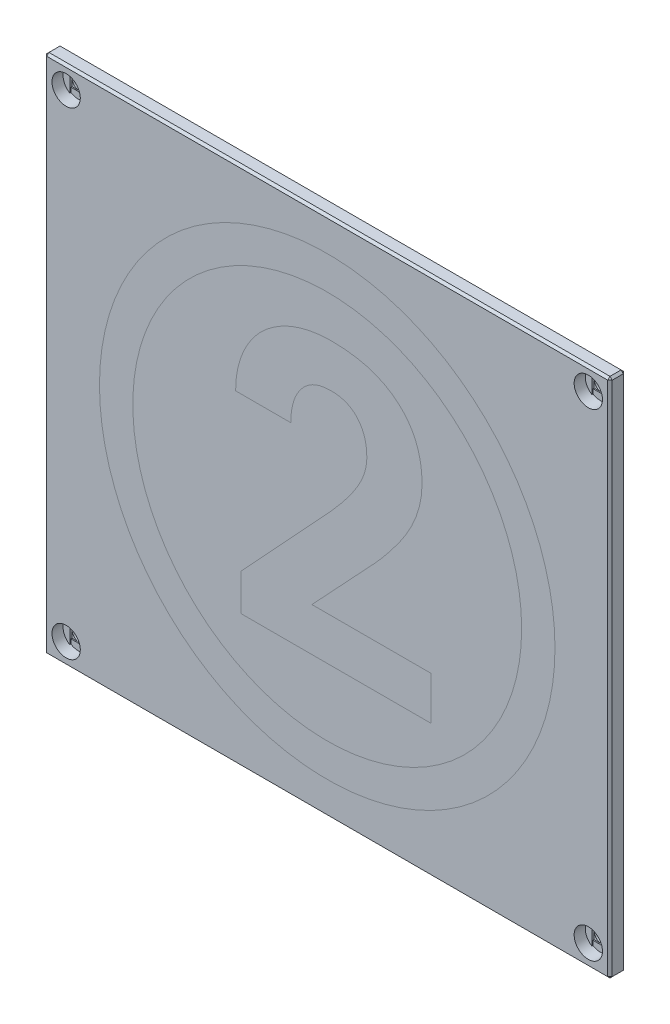
SolidWorks part; units mm, degrees
ref_plane "Front Plane" through (0, 0, 0) normal (0, 0, 1) x (1, 0, 0)
ref_plane "Top Plane" through (0, 0, 0) normal (0, 1, 0) x (1, 0, 0)
ref_plane "Right Plane" through (0, 0, 0) normal (1, 0, 0) x (0, 0, -1)
sketch "Sketch1" plane through (0, 0, 0) normal (0, 0, 1) x (1, 0, 0)
  line L0 (51, 41) -> (43, 41) construction
  line L1 (51, 33) -> (51, 41) construction
  line L2 (51, -53) -> (51, -45) construction
  line L3 (43, -53) -> (51, -53) construction
  line L4 (-51, -53) -> (-43, -53) construction
  line L5 (-51, -45) -> (-51, -53) construction
  line L6 (-51, 41) -> (-51, 33) construction
  line L7 (-43, 41) -> (-51, 41) construction
  line L8 (51, 41) -> (43, 41)
  line L9 (51, 33) -> (51, 41)
  line L10 (51, -53) -> (51, -45)
  line L11 (43, -53) -> (51, -53)
  line L12 (-51, -53) -> (-43, -53)
  line L13 (-51, -45) -> (-51, -53)
  line L14 (-51, 41) -> (-51, 33)
  line L15 (-43, 41) -> (-51, 41)
  circle A0 centre (47, 37) radius 2.15 construction
  circle A1 centre (47, -49) radius 2.15 construction
  circle A2 centre (-47, -49) radius 2.15 construction
  circle A3 centre (-47, 37) radius 2.15 construction
  circle A4 centre (47, 37) radius 2.15
  circle A5 centre (47, -49) radius 2.15
  circle A6 centre (-47, -49) radius 2.15
  circle A7 centre (-47, 37) radius 2.15
sketch "Sketch2" plane through (0, 0, 0) normal (0, 0, 1) x (1, 0, 0)
  line L0 (-51, 41) -> (-51, 33) construction
  line L1 (-50.9, 40.9) -> (50.9, 40.9)
  line L2 (-50.9, 40.9) -> (-50.9, -52.9)
  line L3 (-50.9, -52.9) -> (50.9, -52.9)
  line L4 (50.9, 40.9) -> (50.9, -52.9)
  line L5 (-43, 41) -> (-51, 41) construction
  line L6 (-51, -53) -> (-43, -53) construction
  line L7 (51, -53) -> (51, -45) construction
  circle A0 centre (-47, 37) radius 1.35
  circle A1 centre (47, 37) radius 1.35
  circle A2 centre (47, -49) radius 1.35
  circle A3 centre (-47, -49) radius 1.35
  point P12 (51, -49)
  dimension "D5" = 2.7
  dimension "D1" = 0.1
  dimension "D2" = 0.1
  dimension "D3" = 0.1
  dimension "D4" = 0.1
extrude "Boss-Extrude1" add sketch "Sketch2" along normal blind 2.8
sketch "Sketch3" plane through (0, 0, 2.8) normal (0, 0, 1) x (1, 0, 0)
  circle A0 centre (-47, 37) radius 2.55
  circle A1 centre (47, 37) radius 2.55
  circle A2 centre (47, -49) radius 2.55
  circle A3 centre (-47, -49) radius 2.55
  dimension "D1" = 5.1
extrude "Cut-Extrude1" cut sketch "Sketch3" against normal blind 2
sketch "Sketch4" plane through (0, 0, 0.8) normal (0, 0, 1) x (1, 0, 0)
  line L2 (-48.35, 34.8367) -> (-48.35, 39.1633)
  line L4 (-45.65, 34.8367) -> (-45.65, 39.1633)
  line L5 (-48.35, 34.8367) -> (-45.65, 39.1633) construction
  line L6 (-48.35, 39.1633) -> (-45.65, 34.8367) construction
  circle A0 centre (-47, 37) radius 2.55 construction
  circle A1 centre (-47, 37) radius 1.35 construction
  arc A2 (-45.65, 39.1633) -> (-48.35, 39.1633) centre (-47, 37) ccw
  arc A3 (-48.35, 34.8367) -> (-45.65, 34.8367) centre (-47, 37) ccw
  point P0 (-47, 37)
extrude "Cut-Extrude2" cut sketch "Sketch4" against normal blind 0.2
sketch "Sketch5" plane through (0, 0, 0.6) normal (0, 0, 1) x (1, 0, 0)
  line L0 (-45.65, 34.8367) -> (-45.65, 39.1633) construction
  line L1 (-48.35, 35.65) -> (-45.65, 35.65)
  line L2 (-48.35, 35.65) -> (-48.35, 38.35)
  line L3 (-48.35, 38.35) -> (-45.65, 38.35)
  line L4 (-45.65, 35.65) -> (-45.65, 38.35)
  line L5 (-48.35, 35.65) -> (-45.65, 38.35) construction
  line L6 (-48.35, 38.35) -> (-45.65, 35.65) construction
  arc A0 (-48.35, 37) -> (-45.65, 37) centre (-47, 37) ccw construction
  point P0 (-47, 37)
extrude "Cut-Extrude3" cut sketch "Sketch5" against normal blind 0.2
ref_plane "Plane1" through (0, -6, 0) normal (0, 1, 0) x (1, 0, 0)
mirror "Mirror1" about plane through (0, -6, 0) normal (0, 1, 0) of "Cut-Extrude3", "Cut-Extrude2"
mirror "Mirror2" about plane through (0, 0, 0) normal (1, 0, 0) of "Mirror1"
chamfer "Chamfer1" distance 0.4 angle 45 12 edges at (-50.9, -52.9, 1.4) (50.9, -52.9, 1.4) (50.9, 40.9, 1.4) (0, 40.9, 0) (50.9, -6, 0) (0, -52.9, 0) (-50.9, -6, 0) (-50.9, 40.9, 1.4) (50.9, -6, 2.8) (0, -52.9, 2.8) (-50.9, -6, 2.8) (0, 40.9, 2.8)
sketch "Sketch6" plane through (0, 0, 0) normal (0, 0, -1) x (-1, 0, 0)
  line L0 (-50.9, -52.5) -> (-50.9, 40.5) construction
  line L1 (-40.9, 30.9) -> (40.9, 30.9)
  line L2 (-40.9, 30.9) -> (-40.9, -42.9)
  line L3 (-40.9, -42.9) -> (40.9, -42.9)
  line L4 (40.9, 30.9) -> (40.9, -42.9)
  line L5 (-50.5, 40.9) -> (50.5, 40.9) construction
  line L6 (50.9, 40.5) -> (50.9, -52.5) construction
  line L7 (50.5, -52.9) -> (-50.5, -52.9) construction
  dimension "D1" = 10
  dimension "D2" = 10
  dimension "D3" = 10
  dimension "D4" = 10
extrude "Cut-Extrude4" cut sketch "Sketch6" against normal offset from surface (1.2 mm away) 1.6 up to face at (0, -6, 2.8)
sketch "Sketch7" plane through (0, 0, 2.8) normal (0, 0, 1) x (1, 0, 0)
  line L0 (-47, 37) -> (47, -49) construction
  circle A0 centre (0, -6) radius 41
  circle A1 centre (0, -6) radius 35
  dimension "D1" = 70
  dimension "D2" = 6
extrude "Cut-Extrude5" cut sketch "Sketch7" against normal blind 1
extrude "Boss-Extrude2" add sketch "Sketch7<2>" against normal up to surface (1 mm away) separate body up to face at (35, -6, 1.8)
sketch "Sketch7<2>" plane through (0, 0, 2.8) normal (0, 0, 1) x (1, 0, 0) same geometry as "Sketch7"
sketch "Sketch8" plane through (0, 0, 2.8) normal (0, 0, 1) x (1, 0, 0)
  line L0 (-18.9, -28.9) -> (21.1, -28.9) construction
  line L1 (50.5, -52.9) -> (-50.5, -52.9) construction
  line L2 (-50.9, -52.5) -> (-50.9, 40.5) construction
  text T0 "2" font "Roboto" height 50
  dimension "D1" = 24
  dimension "D2" = 40
  dimension "D3" = 32
extrude "Cut-Extrude6" cut sketch "Sketch8" against normal blind 1
extrude "Boss-Extrude3" add sketch "Sketch8<2>" against normal up to surface (1 mm away) separate body up to face at (0.4994, -5.6463, 1.8)
sketch "Sketch8<2>" plane through (0, 0, 2.8) normal (0, 0, 1) x (1, 0, 0) same geometry as "Sketch8"
